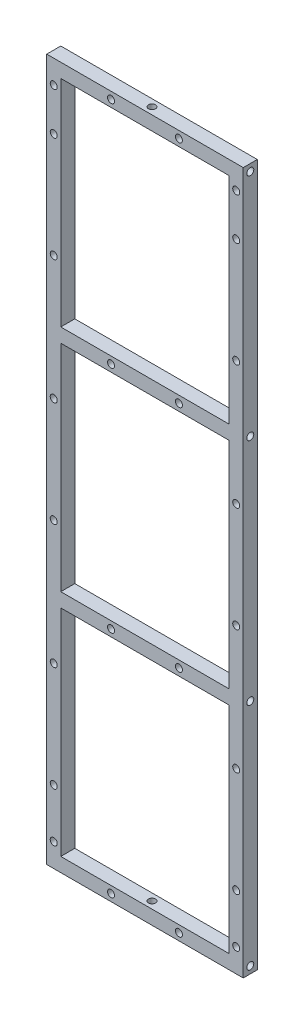
SolidWorks part; units mm, degrees
ref_plane "Front Plane" through (0, 0, 0) normal (0, 0, 1) x (1, 0, 0)
ref_plane "Top Plane" through (0, 0, 0) normal (0, 1, 0) x (1, 0, 0)
ref_plane "Right Plane" through (0, 0, 0) normal (1, 0, 0) x (0, 0, -1)
sketch "Sketch1" plane through (0, 0, 0) normal (0, 0, 1) x (1, 0, 0)
  line L0 (36, 144) -> (36, 52)
  line L9 (-42, -150) -> (42, -150)
  line L10 (-42, -150) -> (-42, 150)
  line L11 (-42, 150) -> (42, 150)
  line L12 (42, -150) -> (42, 150)
  line L15 (-36, -144) -> (36, -144)
  line L16 (-36, -144) -> (-36, -52)
  line L17 (-36, 144) -> (36, 144)
  line L21 (-36, 52) -> (36, 52)
  line L23 (-36, 46) -> (36, 46)
  line L25 (-36, -46) -> (36, -46)
  line L27 (-36, -52) -> (36, -52)
  line L33 (36, 46) -> (36, -46)
  line L34 (-36, 52) -> (-36, 144)
  line L35 (-36, -46) -> (-36, 46)
  line L36 (36, -52) -> (36, -144)
  point P0 (0, 0)
  point P4 (0, -46)
  point P6 (0, 0)
  point P20 (0, 0)
  point P21 (0, -150)
  dimension "D1" = 84
  dimension "D2" = 300
  dimension "D3" = 72
  dimension "D4" = 288
  dimension "D5" = 6
  dimension "D6" = 92
  dimension "D7" = 6
  dimension "D8" = 92
  dimension "D9" = 6
  dimension "D10" = 6
  dimension "D11" = 92
extrude "Boss-Extrude1" add sketch "Sketch1" along normal blind 6
sketch "Sketch2" plane through (42, 0, 0) normal (1, 0, 0) x (0, 0, -1)
  line L0 (-6, 150) -> (0, 150) construction
  circle A0 centre (-3, 147) radius 1.5
  circle A1 centre (-3, 49) radius 1.5
  circle A2 centre (-3, -49) radius 1.5
  circle A3 centre (-3, -147) radius 1.5
  dimension "D1" = 3
  dimension "D2" = 4
extrude "Cut-Extrude1" cut sketch "Sketch2" against normal blind 10
mirror "Mirror1" about plane through (0, 0, 0) normal (1, 0, 0) of "Cut-Extrude1"
sketch "Sketch3" plane through (0, 0, 6) normal (0, 0, 1) x (1, 0, 0)
  line L0 (-42, 150) -> (42, 150) construction
  line L1 (-42, -150) -> (-42, 150) construction
  circle A0 centre (-39, 140) radius 1.5
  circle A1 centre (39, 140) radius 1.5
  circle A2 centre (39, -140) radius 1.5
  circle A3 centre (-39, -140) radius 1.5
  dimension "D1" = 10
  dimension "D2" = 3
  dimension "D3" = 2
  dimension "D4" = 2
extrude "Cut-Extrude2" cut sketch "Sketch3" against normal blind 10
sketch "Sketch4" plane through (0, 0, 6) normal (0, 0, 1) x (1, 0, 0)
  line L0 (-42, -150) -> (-42, 150) construction
  line L1 (42, -150) -> (42, 150) construction
  line L2 (-42, 150) -> (42, 150) construction
  circle A0 centre (-14.5, 147) radius 1.5
  circle A1 centre (14.5, 147) radius 1.5
  circle A2 centre (14.5, 49) radius 1.5
  circle A3 centre (-14.5, 49) radius 1.5
  circle A4 centre (14.5, -49) radius 1.5
  circle A5 centre (-14.5, -49) radius 1.5
  circle A6 centre (14.5, -147) radius 1.5
  circle A7 centre (-14.5, -147) radius 1.5
  circle A8 centre (-39, 122) radius 1.5
  circle A9 centre (-39, 77) radius 1.5
  circle A10 centre (39, 122) radius 1.5
  circle A11 centre (39, 77) radius 1.5
  circle A12 centre (39, 24) radius 1.5
  circle A13 centre (39, -21) radius 1.5
  circle A14 centre (39, -74) radius 1.5
  circle A15 centre (39, -119) radius 1.5
  circle A16 centre (-39, 24) radius 1.5
  circle A17 centre (-39, -21) radius 1.5
  circle A18 centre (-39, -74) radius 1.5
  circle A19 centre (-39, -119) radius 1.5
  dimension "D1" = 27.5
  dimension "D4" = 45
  dimension "D7" = 2
  dimension "D2" = 27.5
  dimension "D3" = 4
  dimension "D5" = 28
  dimension "D6" = 28
  dimension "D9" = 3
  dimension "D8" = 3
extrude "Cut-Extrude3" cut sketch "Sketch4" against normal blind 10
sketch "Sketch5" plane through (0, 150, 0) normal (0, 1, 0) x (1, 0, 0)
  line L0 (42, -6) -> (-42, -6) construction
  circle A0 centre (0, -3) radius 1.5
  point P5 (0, -6)
  dimension "D1" = 3
extrude "Cut-Extrude4" cut sketch "Sketch5" against normal blind 10
mirror "Mirror2" about plane through (0, 0, 0) normal (0, 1, 0) of "Cut-Extrude4"
